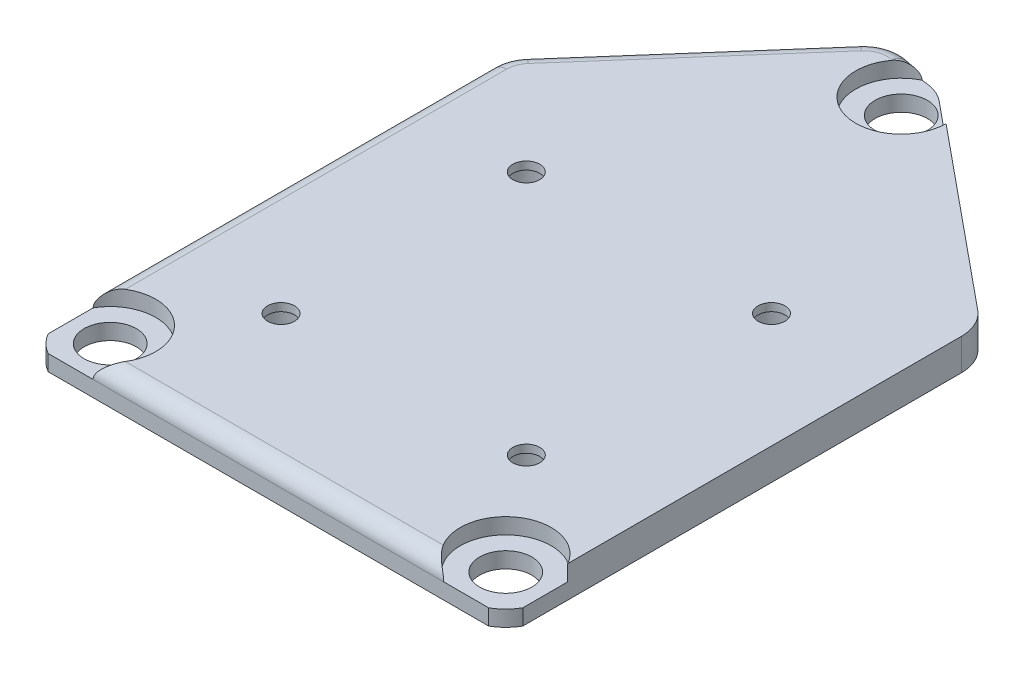
SolidWorks part; units mm, degrees
ref_plane "Front Plane" through (0, 0, 0) normal (0, 0, 1) x (1, 0, 0)
ref_plane "Top Plane" through (0, 0, 0) normal (0, 1, 0) x (1, 0, 0)
ref_plane "Right Plane" through (0, 0, 0) normal (1, 0, 0) x (0, 0, -1)
sketch "Sketch1" plane through (0, 0, 0) normal (0, 1, 0) x (1, 0, 0)
  line L0 (0, 0) -> (0, -72.4) construction
  circle A0 centre (0, -72.4) radius 6.3405 construction
  point P4 (25, -100)
  point P7 (-25, -100)
  point P17 (0, -25)
  dimension "D1" = 72.4
  dimension "D2" = 25
  dimension "D3" = 100
  dimension "D5" = 25
sketch "Sketch2" plane through (0, 0, 0) normal (0, 1, 0) x (1, 0, 0)
  line L0 (-30, -45) -> (-6.9921, -18.738)
  line L6 (0, 0) -> (0, -72.4) construction
  line L7 (0, -75) -> (0, -52.0117) construction
  line L9 (-30, -105) -> (30, -105)
  line L10 (-30, -105) -> (-30, -45)
  line L12 (30, -105) -> (30, -45)
  line L13 (-30, -105) -> (30, -45) construction
  line L14 (-30, -45) -> (30, -105) construction
  line L15 (-0.4369, -19.9952) -> (30, -45)
  arc A0 (-6.9921, -18.738) -> (-0.4369, -19.9952) centre (0, 0) ccw
  point P14 (0, -75)
  point P15 (0, -75)
  dimension "D2" = 20
  dimension "D1" = 25
  dimension "D3" = 60
  dimension "D4" = 60
extrude "Boss-Extrude1" add sketch "Sketch2" along normal blind 4 contours L10 L0 A0 L15 L12 L9
hole_wizard "Hole1" positions "Sketch3" profile "Sketch4" legacy end condition up to next
sketch "Sketch3" plane through (0, 4, 0) normal (0, 1, 0) x (1, 0, 0)
  point P4 (-25, -100)
  point P6 (25, -100)
  point P14 (0, -25)
sketch "Sketch4" plane through (-25, 4, 100) normal (1, 0, 0) x (0, 0, 1)
  line L0 (0, 0) -> (0, 4)
  line L1 (0, 4) -> (3.3, 4)
  line L3 (3.3, 4) -> (3.3, 2)
  line L4 (3.3, 2) -> (5.75, 2)
  line L5 (5.75, 2) -> (5.75, 0)
  line L7 (5.75, 0) -> (0, 0)
  line L11 (0, -6.35) -> (0, 107.95) construction
  dimension "Thru Hole Dia." = 6.6
  dimension "Thru Hole Depth" = 4
  dimension "C'Bore Dia." = 11.5
  dimension "C'Bore Depth" = 2
sketch "Sketch5" plane through (0, 4, 0) normal (0, 1, 0) x (1, 0, 0)
  line L0 (-30, -105) -> (-27.8395, -105) construction
  line L5 (-30, -102.8395) -> (-30, -105)
  line L6 (-30, -105) -> (-27.8395, -105)
  line L11 (0, -105) -> (0, -90.3325) construction
  line L12 (-22.1605, -105) -> (22.1605, -105) construction
  line L13 (30, -105) -> (27.8395, -105)
  line L14 (30, -102.8395) -> (30, -105)
  arc A0 (-30, -102.8395) -> (-27.8395, -105) centre (-25, -100) ccw
  arc A1 (30, -102.8395) -> (27.8395, -105) centre (25, -100) cw
extrude "Cut-Extrude3" cut sketch "Sketch5" against normal through all
sketch "Sketch6" plane through (0, 0, 0) normal (0, -1, 0) x (1, 0, 0)
  line L0 (0, 0) -> (0, 72.4) construction
  point P0 (-15.5, 56.9)
  point P5 (0, 72.4)
  point P8 (-15.5, 87.9)
  point P9 (15.5, 87.9)
  point P10 (15.5, 56.9)
  point P11 (0, 72.4)
  dimension "D1" = 15.5
  dimension "D2" = 15.5
  dimension "D3" = 4
hole_wizard "CBORE for M3 SHCS1" positions "Sketch7" profile "Sketch8" counterbore size "M3" standard "ANSI Metric" end condition through all
sketch "Sketch7" plane through (0, 0, 0) normal (0, -1, 0) x (-1, 0, 0)
  point P0 (-15.5, -56.9)
  point P3 (15.5, -56.9)
  point P6 (15.5, -87.9)
  point P9 (-15.5, -87.9)
sketch "Sketch8" plane through (15.5, 0, 56.9) normal (1, 0, 0) x (0, 0, -1)
  line L0 (0, 0) -> (0, 4)
  line L1 (0, 4) -> (1.7, 4)
  line L3 (1.7, 4) -> (1.7, 3)
  line L4 (1.7, 3) -> (3.25, 3)
  line L5 (3.25, 3) -> (3.25, 0)
  line L7 (3.25, 0) -> (0, 0)
  line L11 (0, -6.35) -> (0, 107.95) construction
  dimension "Thru Hole Dia." = 3.4
  dimension "Thru Hole Depth" = 4
  dimension "C'Bore Dia." = 6.5
  dimension "C'Bore Depth" = 3
fillet "Fillet4" radius 5 4 edges at (-30, 2, 45) (-6.9921, 2, 18.738) (-0.4369, 1, 19.9952) (30, 2, 45)
fillet "Fillet3" radius 2 6 edges at (0, 4, 105) (-30, 4, 72.0205) (-18.9247, 4, 32.3582) (-29.68, 4, 45.1204) (-3.4016, 4, 19.7086) (-6.8924, 4, 19.6769)
